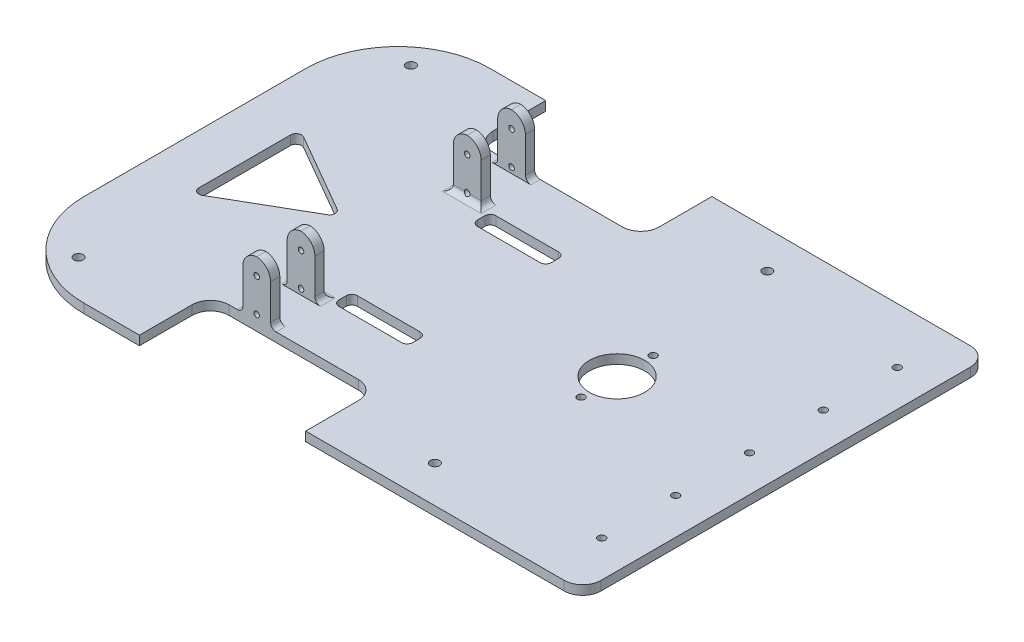
SolidWorks part; units mm, degrees
ref_plane "Front Plane" through (0, 0, 0) normal (0, 0, 1) x (1, 0, 0)
ref_plane "Top Plane" through (0, 0, 0) normal (0, 1, 0) x (1, 0, 0)
ref_plane "Right Plane" through (0, 0, 0) normal (1, 0, 0) x (0, 0, -1)
sketch "Sketch1" plane through (0, 0, 0) normal (0, 1, 0) x (1, 0, 0)
  line L1 (-160, 110) -> (160, 110)
  line L2 (-160, 110) -> (-160, -110)
  line L3 (-160, -110) -> (160, -110)
  line L4 (160, 110) -> (160, -110)
  line L5 (-160, 110) -> (160, -110) construction
  line L6 (-160, -110) -> (160, 110) construction
  point P1 (0, 0)
  dimension "D1" = 320
  dimension "D2" = 220
extrude "Boss-Extrude1" add sketch "Sketch1" along normal mid plane 5
sketch "Sketch2" plane through (0, 0, 0) normal (0, 1, 0) x (1, 0, 0)
  line L0 (0, 110) -> (0, -110) construction
  line L1 (160, 110) -> (-160, 110) construction
  line L2 (-160, -110) -> (160, -110) construction
  line L3 (160, 0) -> (-160, 0) construction
  line L4 (160, -110) -> (160, 110) construction
  line L5 (-160, 110) -> (-160, -110) construction
  line L6 (-133, 90) -> (-133, 0) construction
  line L7 (-133, -90) -> (-133, 0) construction
  line L8 (-160, 110) -> (-160, -110) construction
  line L10 (60, 90) -> (60, -90) construction
  line L11 (160, -110) -> (160, 110) construction
  circle A0 centre (-133, 90) radius 2.5
  circle A1 centre (-133, -90) radius 2.5
  circle A2 centre (60, 90) radius 2.5
  circle A3 centre (60, -90) radius 2.5
  dimension "D2" = 5
  dimension "D3" = 5
  dimension "D5" = 5
  dimension "D6" = 5
  dimension "D1" = 20
  dimension "D4" = 27
  dimension "D7" = 100
extrude "Cut-Extrude1" cut sketch "Sketch2" along direction (0, 1, 0) on the side against the normal mid plane 5
fillet "Fillet5" radius 50 2 edges at (-160, 0, -110) (-160, 0, 110)
sketch "Sketch3" plane through (0, 0, 0) normal (0, 1, 0) x (1, 0, 0)
  line L0 (160, 0) -> (-160, 0) construction
  line L1 (160, -110) -> (160, 110) construction
  line L2 (-160, 60) -> (-160, -60) construction
  line L3 (-80, 110) -> (-80, 71.5023)
  line L4 (160, 110) -> (-110, 110) construction
  line L5 (-80, 71.5023) -> (10, 71.5023)
  line L6 (10, 71.5023) -> (10, 110)
  line L7 (10, 110) -> (-80, 110)
  line L8 (10, -71.5023) -> (10, -110)
  line L9 (-80, -110) -> (-80, -71.5023)
  line L10 (-80, -71.5023) -> (10, -71.5023)
  line L11 (10, -110) -> (-80, -110)
  dimension "D1" = 90
  dimension "D2" = 80
extrude "Cut-Extrude2" cut sketch "Sketch3" against normal mid plane 5
fillet "Fillet3" radius 10 4 edges at (10, 0, 71.5023) (-80, 0, 71.5023) (-80, 0, -71.5023) (10, 0, -71.5023)
sketch "Sketch4" plane through (0, 0, 0) normal (0, 1, 0) x (1, 0, 0)
  line L0 (160, 0) -> (-160, 0) construction
  line L1 (160, -110) -> (160, 110) construction
  line L2 (-160, 60) -> (-160, -60) construction
  line L6 (68.6574, 19.5) -> (68.6574, 0) construction
  line L7 (68.6574, 0) -> (68.6574, -19.5) construction
  circle A0 centre (68.6574, 0) radius 15
  circle A1 centre (68.6574, 19.5) radius 2
  circle A2 centre (68.6574, -19.5) radius 2
  dimension "D1" = 30
  dimension "D2" = 2
  dimension "D3" = 4
  dimension "D4" = 39
extrude "middle hole" cut sketch "Sketch4" against normal mid plane 5
sketch "Sketch6" plane through (0, 0, 0) normal (0, 1, 0) x (1, 0, 0)
  line L0 (160, 0) -> (-160, 0) construction
  line L1 (160, -110) -> (160, 110) construction
  line L2 (-160, 60) -> (-160, -60) construction
  circle A0 centre (140.3612, 0) radius 2
  dimension "D1" = 4
extrude "Cut-Extrude4" cut sketch "Sketch6" against normal mid plane 5
pattern_linear "LPattern1" count 3 spacing 40 along (0, 0, -1) of "Cut-Extrude4"
pattern_linear "LPattern2" count 3 spacing 40 along (0, 0, 1) of "Cut-Extrude4"
sketch "Sketch8" plane through (0, 2.5, 0) normal (0, 1, 0) x (1, 0, 0)
  line L0 (0, -71.5023) -> (-70, -71.5023) construction
  line L1 (-62.5, -71.5023) -> (-47.5, -71.5023)
  line L2 (-62.5, -71.5023) -> (-62.5, -66.5023)
  line L3 (-62.5, -66.5023) -> (-47.5, -66.5023)
  line L4 (-47.5, -71.5023) -> (-47.5, -66.5023)
  line L6 (160, 0) -> (-160, 0) construction
  line L7 (160, -110) -> (160, 110) construction
  line L8 (-160, 60) -> (-160, -60) construction
  line L13 (-160, -47.5023) -> (160, -47.5023) construction
  line L14 (160, -110) -> (160, 110) construction
  line L15 (-55, -66.5023) -> (-55, -47.5023) construction
  line L16 (-55, -57.0023) -> (-160, -57.0023) construction
  line L17 (-47.5, -42.5023) -> (-47.5, -47.5023)
  line L18 (-62.5, -47.5023) -> (-47.5, -47.5023)
  line L19 (-62.5, -42.5023) -> (-62.5, -47.5023)
  line L20 (-62.5, -42.5023) -> (-47.5, -42.5023)
  line L21 (-55, 57.0023) -> (-160, 57.0023) construction
  line L22 (-55, 66.5023) -> (-55, 47.5023) construction
  line L23 (-160, 47.5023) -> (160, 47.5023) construction
  line L24 (-62.5, 42.5023) -> (-47.5, 42.5023)
  line L25 (-62.5, 42.5023) -> (-62.5, 47.5023)
  line L26 (-62.5, 47.5023) -> (-47.5, 47.5023)
  line L27 (-47.5, 42.5023) -> (-47.5, 47.5023)
  line L28 (-47.5, 71.5023) -> (-47.5, 66.5023)
  line L29 (-62.5, 66.5023) -> (-47.5, 66.5023)
  line L30 (-62.5, 71.5023) -> (-62.5, 66.5023)
  line L31 (-62.5, 71.5023) -> (-47.5, 71.5023)
  line L32 (10, -110) -> (-80, -110) construction
  line L33 (-35, -110) -> (-35, 0) construction
  point P22 (-55, -66.5023)
  point P47 (-55, -71.5023)
  dimension "D1" = 5
  dimension "D3" = 15
  dimension "D4" = 19
  dimension "D5" = 20
  dimension "D2" = 27.5
extrude "Boss-Extrude2" add sketch "Sketch8" along normal blind 30
sketch "Sketch10" plane through (0, 0, 0) normal (0, 1, 0) x (1, 0, 0)
  line L0 (10, -110) -> (10, -81.5023) construction
  line L1 (-42.5, -32.5023) -> (-2.5, -32.5023)
  line L2 (-42.5, -32.5023) -> (-42.5, -42.5023)
  line L3 (-42.5, -42.5023) -> (-2.5, -42.5023)
  line L4 (-2.5, -32.5023) -> (-2.5, -42.5023)
  line L5 (-160, 60) -> (-160, -60) construction
  line L6 (-160, 0) -> (160, 0) construction
  line L7 (160, -110) -> (160, 110) construction
  line L8 (-2.5, 32.5023) -> (-2.5, 42.5023)
  line L9 (-42.5, 42.5023) -> (-2.5, 42.5023)
  line L10 (-42.5, 32.5023) -> (-42.5, 42.5023)
  line L11 (-42.5, 32.5023) -> (-2.5, 32.5023)
  line L13 (-47.5, -47.5023) -> (-47.5, -42.5023) construction
  point P4 (-244.8991, -6.729)
  dimension "D1" = 5
  dimension "D3" = 40
  dimension "D4" = 10
extrude "Cut-Extrude6" cut sketch "Sketch10" against normal mid plane 67.5
sketch "Sketch9" plane through (0, 0, 71.5023) normal (0, 0, 1) x (1, 0, 0)
  line L0 (-55, 32.5) -> (-55, -2.5) construction
  line L1 (-62.5, 32.5) -> (-47.5, 32.5) construction
  line L2 (0, -2.5) -> (-70, -2.5) construction
  line L3 (0, 2.5) -> (-47.5, 2.5) construction
  circle A0 centre (-55, 23.5) radius 1.5
  circle A1 centre (-55, 5.5) radius 1.5
  dimension "D1" = 3
  dimension "D2" = 3
  dimension "D3" = 3
  dimension "D4" = 18
extrude "Cut-Extrude5" cut sketch "Sketch9" against normal up to surface (143.0046 mm away) up to face at (-45, 8.75, -71.5023)
fillet "Fillet6" radius 8 8 edges at (-62.5, 32.5, 69.0023) (-47.5, 32.5, 69.0023) (-47.5, 32.5, -69.0023) (-62.5, 32.5, -69.0023) (-62.5, 32.5, -45.0023) (-47.5, 32.5, -45.0023) (-47.5, 32.5, 45.0023) (-62.5, 32.5, 45.0023)
fillet "Fillet7" radius 10 2 edges at (160, 0, 110) (160, 0, -110)
fillet "Fillet8" radius 3 8 edges at (-42.5, 0, 32.5023) (-42.5, 0, 42.5023) (-42.5, 0, -42.5023) (-42.5, 0, -32.5023) (-2.5, 0, -32.5023) (-2.5, 0, 32.5023) (-2.5, 0, -42.5023) (-2.5, 0, 42.5023)
sketch "Sketch11" plane through (0, 0, 0) normal (0, 1, 0) x (1, 0, 0)
  line L0 (-160, 0) -> (160, 0) construction
  line L1 (-160, 60) -> (-160, -60) construction
  line L2 (160, -100) -> (160, 100) construction
  line L3 (-81.0385, 0) -> (-133, 30)
  line L4 (-133, 30) -> (-133, -30)
  line L5 (-133, -30) -> (-81.0385, 0)
  line L6 (-133, 90) -> (-133, -90) construction
  dimension "D1" = 60
extrude "Cut-Extrude7" cut sketch "Sketch11" against normal mid plane 10
fillet "Fillet9" radius 3 3 edges at (-133, 0, 30) (-133, 0, -30) (-81.0385, 0, 0)
sketch "Sketch12" plane through (0, 0, 0) normal (0, 1, 0) x (1, 0, 0)
  line L0 (-133, 90) -> (-133, -90) construction
fillet "Fillet10" radius 3 10 edges at (-62.5, 2.5, -45.0023) (-62.5, 2.5, -69.0023) (-55, 2.5, -42.5023) (-55, 2.5, 42.5023) (-62.5, 2.5, 45.0023) (-47.5, 2.5, 45.0023) (-47.5, 2.5, -69.0023) (-47.5, 2.5, -45.0023) (-62.5, 2.5, 69.0023) (-47.5, 2.5, 69.0023)
equation "\"carW\"= 22cm"
equation "\"carL\"= 32cm"
equation "\"D1@Sketch1\"=\"carL\""
equation "\"D2@Sketch1\"=\"carW\""
equation "\"carT\"= .5cm'car thickness"
equation "\"D1@Boss-Extrude1\"=\"carT\""
equation "\"linkNialDim\"= 0.5cm"
equation "\"D2@Sketch2\"=\"linkNialDim\""
equation "\"D3@Sketch2\"=\"linkNialDim\""
equation "\"D1@Sketch8\"=\"carT\""
equation "\"D5@Sketch2\"=\"linkNialDim\""
equation "\"D6@Sketch2\"=\"linkNialDim\""
